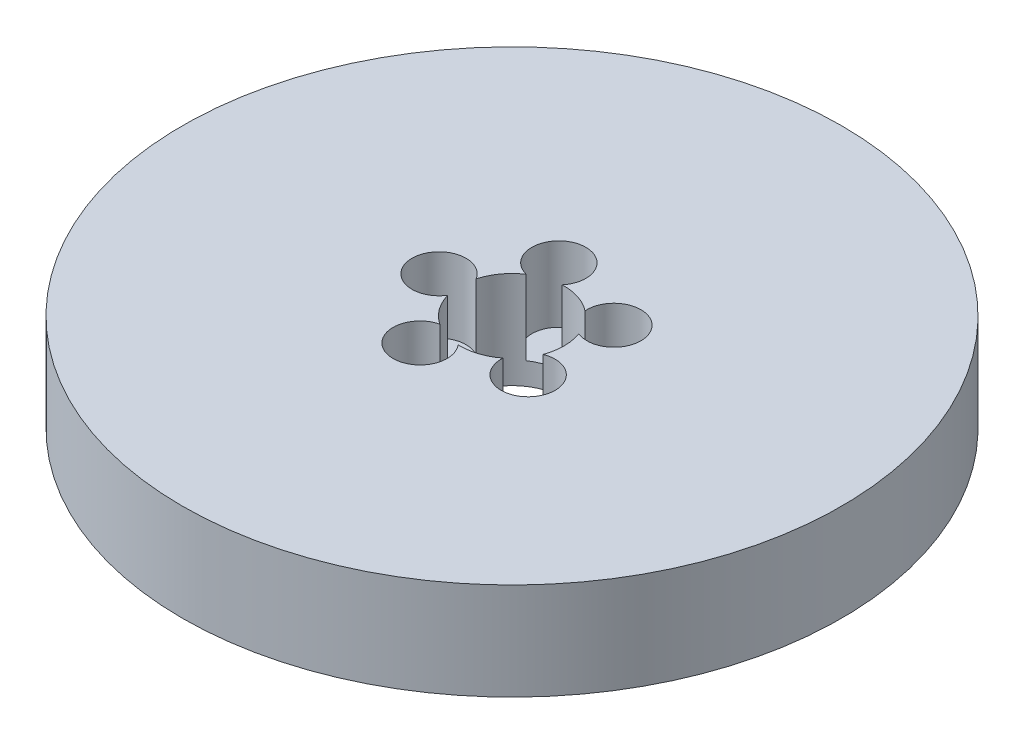
SolidWorks part; units mm, degrees
ref_plane "Front Plane" through (0, 0, 0) normal (0, 0, 1) x (1, 0, 0)
ref_plane "Top Plane" through (0, 0, 0) normal (0, 1, 0) x (1, 0, 0)
ref_plane "Right Plane" through (0, 0, 0) normal (1, 0, 0) x (0, 0, -1)
sketch "Sketch1" plane through (0, 0, 0) normal (0, 1, 0) x (1, 0, 0)
  circle A0 centre (0, 0) radius 47.5
  dimension "FLANGE_OD" = 95
extrude "Boss-Extrude1" add sketch "Sketch1" along normal blind 14
sketch "Sketch2" plane through (0, 0, 0) normal (0, 1, 0) x (1, 0, 0)
  circle A0 centre (0, 0) radius 7.5
  dimension "BORE_D" = 15
extrude "Cut-Extrude1" cut sketch "Sketch2" along normal through all
sketch "Sketch3" plane through (0, 14, 0) normal (0, 1, 0) x (1, 0, 0)
  circle A0 centre (0, 0) radius 10.5157 construction
  circle A1 centre (-10.5157, 0) radius 3.8918
  dimension "BOLT_D" = 7.7835
  dimension "BOLT_PCD" = 21.0315
extrude "Cut-Extrude2" cut sketch "Sketch3" against normal blind 10.7921
pattern_circular "CirPattern1" count 5 over 360 about axis through (0, 0, 0) along (0, 1, 0) of "Cut-Extrude2"
